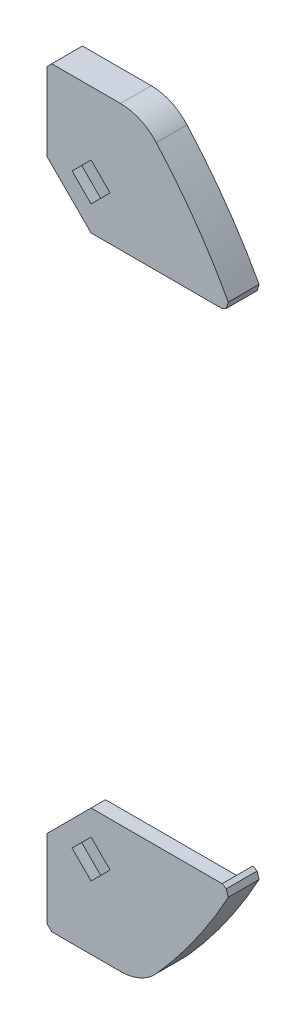
SolidWorks part; units mm, degrees
ref_plane "Front Plane" through (0, 0, 0) normal (0, 0, 1) x (1, 0, 0)
ref_plane "Top Plane" through (0, 0, 0) normal (0, 1, 0) x (1, 0, 0)
ref_plane "Right Plane" through (0, 0, 0) normal (1, 0, 0) x (0, 0, -1)
sketch "Sketch1" plane through (0, 0, 0) normal (0, 0, 1) x (1, 0, 0)
  line L2 (268.6913, 213.5528) -> (338.2149, 213.5528)
  line L3 (268.6913, 213.5528) -> (338.2149, 213.5528)
  line L4 (319.499, 365.9528) -> (319.499, 350.7528)
  line L5 (338.2149, 365.9528) -> (268.6913, 365.9528)
  line L6 (338.684, 365.9528) -> (268.6913, 365.9528)
  line L7 (319.499, 350.7528) -> (328.6913, 341.5604)
  line L8 (328.6913, 341.5604) -> (355.9539, 341.5604)
  line L9 (355.9539, 341.5604) -> (357.7191, 342.5006)
  line L10 (319.499, 365.9528) -> (319.499, 367.9528)
  line L11 (341.4144, 367.9528) -> (268.6913, 367.9528)
  line L12 (338.2149, 365.9528) -> (268.6913, 365.9528) construction
  line L13 (338.2149, 367.9528) -> (268.6913, 367.9528) construction
  line L14 (328.6913, 350.7528) -> (328.6913, 341.5604) construction
  line L15 (319.499, 350.7528) -> (328.6913, 350.7528) construction
  circle A1 centre (328.6913, 350.7528) radius 1.5 construction
  arc A2 (338.3595, 213.6146) -> (338.3595, 365.8909) centre (258.6913, 289.7528) ccw
  arc A3 (338.3595, 213.6146) -> (338.0292, 366.2351) centre (258.6913, 289.7528) ccw
  circle A4 centre (328.6913, 350.7528) radius 1.5
  circle A5 centre (328.6913, 228.7528) radius 1.5 construction
  circle A6 centre (328.6913, 228.7528) radius 1.5
  arc A7 (339.8054, 212.2328) -> (338.3169, 368.8009) centre (258.6913, 289.7528) ccw
  arc A8 (338.3595, 213.6146) -> (338.3595, 365.8909) centre (258.6913, 289.7528) ccw construction
  arc A9 (339.8054, 212.2328) -> (339.8054, 367.2728) centre (258.6913, 289.7528) ccw construction
  dimension "D4" = 2
  dimension "D6" = 45
  dimension "D7" = 5
  dimension "D1" = 0.2
  dimension "D2" = 0.2
  dimension "D3" = 0.2
  dimension "D5" = 2
extrude "Boss-Extrude1" add sketch "Sketch1" along normal up to surface (3 mm away)
sketch "Sketch2" plane through (0, 0, 0) normal (0, 0, -1) x (-1, 0, 0)
  line L0 (-339.15, 367.9528) -> (-319.499, 367.9528) construction
  line L1 (-339.15, 367.9528) -> (-319.499, 367.9528)
  line L2 (-339.15, 365.9528) -> (-319.499, 365.9528)
  line L4 (-355.9539, 341.5604) -> (-357.7191, 342.5006)
  line L5 (-319.499, 350.7528) -> (-319.499, 367.9528) construction
  line L6 (-319.499, 350.7528) -> (-319.499, 367.9528)
  arc A0 (-339.15, 367.9528) -> (-357.7191, 342.5006) centre (-258.6913, 289.7528) ccw construction
  arc A1 (-339.15, 367.9528) -> (-357.7191, 342.5006) centre (-258.6913, 289.7528) ccw
  arc A2 (-337.7158, 366.5588) -> (-355.9539, 341.5604) centre (-258.6913, 289.7528) ccw
  dimension "D1" = 2
  dimension "D2" = 2
extrude "Boss-Extrude2" add sketch "Sketch2" along normal up to surface (3.4 mm away)
sketch "Sketch3" plane through (0, 0, 3) normal (0, 0, 1) x (1, 0, 0)
  line L0 (332.6511, 350.7528) -> (328.6913, 346.793)
  line L1 (332.6511, 350.7528) -> (328.6913, 354.7126)
  line L2 (328.6913, 346.793) -> (324.7315, 350.7528)
  line L3 (328.6913, 354.7126) -> (324.7315, 350.7528)
  line L4 (332.6511, 350.7528) -> (324.7315, 350.7528) construction
  line L5 (328.6913, 346.793) -> (328.6913, 354.7126) construction
  line L6 (319.499, 350.7528) -> (328.6913, 341.5604) construction
  line L7 (117.8913, 361.5528) -> (117.8913, 355.9528) construction
  circle A0 centre (328.6913, 350.7528) radius 1.5 construction
  circle A1 centre (328.6913, 350.7528) radius 1.5 construction
  point P1 (328.6913, 350.7528)
extrude "Cut-Extrude1" cut sketch "Sketch3" against normal up to surface (2 mm away)
fillet "Fillet1" radius 10 1 edges at (339.15, 367.9528, -0.2)
chamfer "Chamfer1" distance 1 angle 45 2 edges at (319.499, 367.9528, -0.2) (357.7191, 342.5006, -0.2)
ref_plane "Plane1" through (0, 289.7528, 0) normal (0, 1, 0) x (1, 0, 0)
mirror "Mirror2" about plane through (0, 289.7528, 0) normal (0, 1, 0) of bodies 103
sketch "Sketch4" plane through (0, 0, 1) normal (0, 0, 1) x (1, 0, 0)
  circle A0 centre (328.6913, 350.7528) radius 1.5 construction
  circle A1 centre (328.6913, 350.7528) radius 1.5
  circle A2 centre (328.6913, 228.7528) radius 1.5 construction
  circle A3 centre (328.6913, 228.7528) radius 1.5
extrude "Boss-Extrude3" add sketch "Sketch4" against normal blind 0.2
